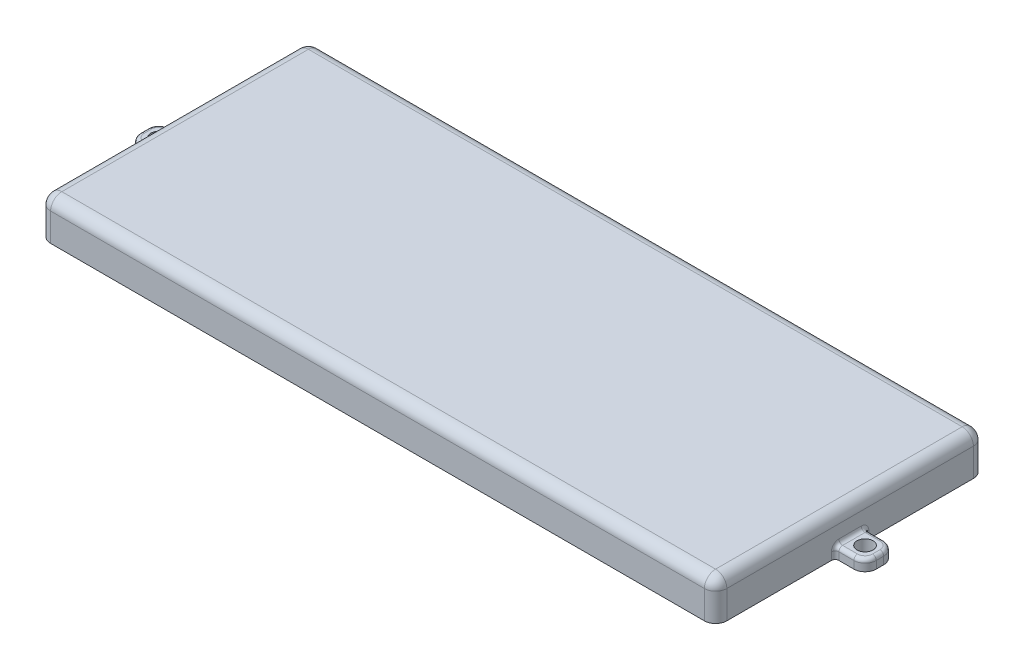
SolidWorks part; units mm, degrees
ref_plane "Front Plane" through (0, 0, 0) normal (0, 0, 1) x (1, 0, 0)
ref_plane "Top Plane" through (0, 0, 0) normal (0, 1, 0) x (1, 0, 0)
ref_plane "Right Plane" through (0, 0, 0) normal (1, 0, 0) x (0, 0, -1)
sketch "Sketch1" plane through (0, 0, 0) normal (0, 1, 0) x (1, 0, 0)
  line L1 (-90.5, 36) -> (90.5, 36)
  line L2 (-90.5, 36) -> (-90.5, -36)
  line L3 (-90.5, -36) -> (90.5, -36)
  line L4 (90.5, 36) -> (90.5, -36)
  line L5 (0, -36) -> (0, 36) construction
  line L6 (-90.5, 0) -> (90.5, 0) construction
  point P0 (0, 0)
  dimension "D1" = 72
  dimension "D2" = 181
extrude "Boss-Extrude1" add sketch "Sketch1" along normal blind 10.5
shell "Shell1" thickness 3 removed face at (0, 0, 0)
sketch "Sketch2" plane through (-90.5, 0, 0) normal (-1, 0, 0) x (0, 0, 1)
  line L0 (-36, 0) -> (36, 0) construction
  line L1 (-4, 0) -> (4, 0)
  line L2 (-4, 0) -> (-4, 3)
  line L3 (-4, 3) -> (4, 3)
  line L4 (4, 0) -> (4, 3)
  line L5 (-36, 10.5) -> (-36, 0) construction
  dimension "D1" = 8
  dimension "D2" = 3
  dimension "D3" = 32
extrude "Boss-Extrude2" add sketch "Sketch2" along normal blind 8
sketch "Sketch3" plane through (90.5, 0, 0) normal (1, 0, 0) x (0, 0, -1)
  line L0 (-36, 0) -> (36, 0) construction
  line L1 (-4, 0) -> (4, 0)
  line L2 (-4, 0) -> (-4, 3)
  line L3 (-4, 3) -> (4, 3)
  line L4 (4, 0) -> (4, 3)
  line L5 (-36, 10.5) -> (-36, 0) construction
  dimension "D1" = 8
  dimension "D2" = 3
  dimension "D3" = 32
extrude "Boss-Extrude3" add sketch "Sketch3" along normal blind 8
sketch "Sketch4" plane through (0, 3, 0) normal (0, 1, 0) x (1, 0, 0)
  line L0 (-98.5, 4) -> (-90.5, -4) construction
  line L1 (-98.5, -4) -> (-90.5, 4) construction
  circle A0 centre (-94.5, 0) radius 2.15
  dimension "D1" = 4.3
extrude "Cut-Extrude1" cut sketch "Sketch4" against normal blind 8
sketch "Sketch5" plane through (0, 3, 0) normal (0, 1, 0) x (1, 0, 0)
  line L0 (90.5, 4) -> (98.5, -4) construction
  line L1 (90.5, -4) -> (98.5, 4) construction
  circle A0 centre (94.5, 0) radius 2.15
  dimension "D1" = 4.3
extrude "Cut-Extrude2" cut sketch "Sketch5" against normal blind 8
fillet "Fillet1" radius 3 20 edges at (-87.5, 3.75, -33) (-87.5, 3.75, 33) (87.5, 3.75, -33) (87.5, 3.75, 33) (98.5, 1.5, 4) (98.5, 1.5, -4) (90.5, 5.25, -36) (90.5, 5.25, 36) (-90.5, 5.25, -36) (-90.5, 5.25, 36) (-98.5, 1.5, -4) (-98.5, 1.5, 4) (0, 10.5, 36) (-90.5, 10.5, 0) (0, 10.5, -36) (90.5, 10.5, 0) (87.5, 7.5, 0) (0, 7.5, -33) (-87.5, 7.5, 0) (0, 7.5, 33)
fillet "Fillet2" radius 1 16 edges at (-90.5, 1.5, -4) (-90.5, 3, 0) (-90.5, 1.5, 4) (90.5, 1.5, 4) (90.5, 1.5, -4) (90.5, 3, 0) (93, 3, 4) (93, 3, -4) (97.6213, 3, -3.1213) (98.5, 3, 0) (-93, 3, 4) (-97.6213, 3, 3.1213) (-93, 3, -4) (-97.6213, 3, -3.1213) (97.6213, 3, 3.1213) (-98.5, 3, 0)
